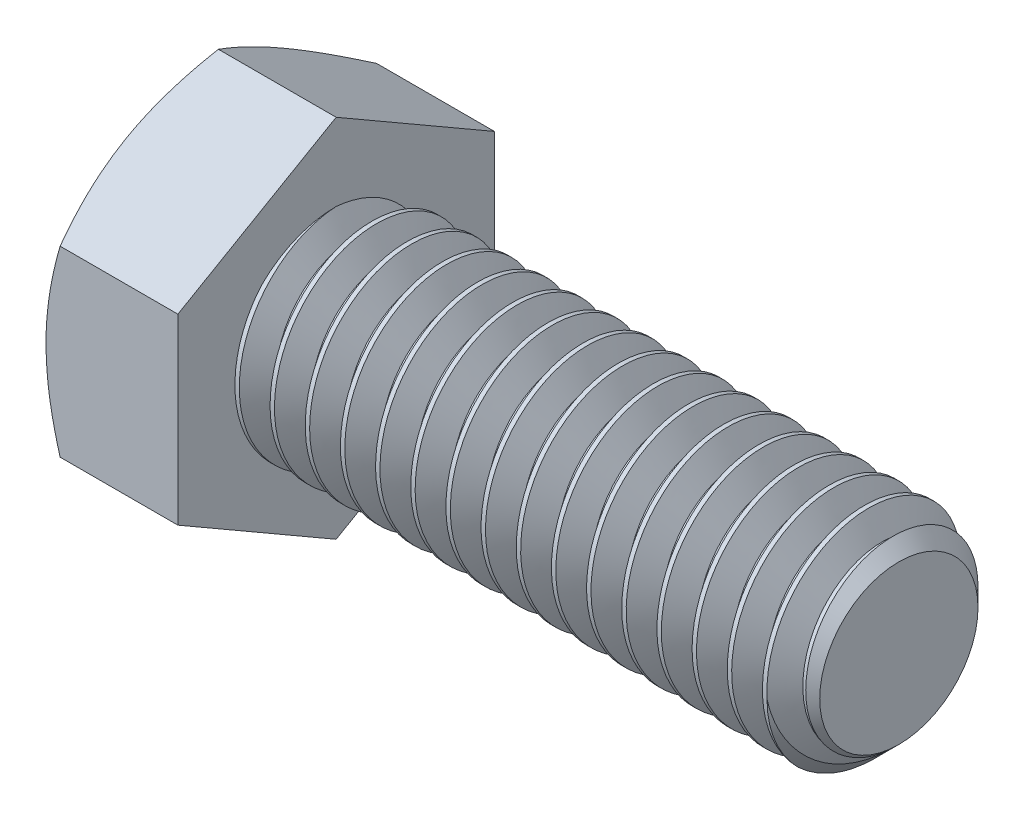
SolidWorks part; units mm, degrees
material "Stainless Steel (ferritic)"
ref_plane "Front Plane" through (0, 0, 0) normal (0, 0, 1) x (1, 0, 0)
ref_plane "Top Plane" through (0, 0, 0) normal (0, 1, 0) x (1, 0, 0)
ref_plane "Right Plane" through (0, 0, 0) normal (1, 0, 0) x (0, 0, -1)
sketch "Sketch1" plane through (0, 0, 0) normal (0, 0, 1) x (1, 0, 0)
  line L0 (-15.6766, 0) -> (15.6766, 0) construction
  line L1 (15.6766, 4.7625) -> (15.6766, -4.7625) construction
  line L2 (-9.7234, 7.1437) -> (-9.7234, -7.1437) construction
  line L3 (-15.6766, 7.1437) -> (-15.6766, -7.1437) construction
  point P9 (-9.7234, 0)
  point P10 (10.1203, -4.7625)
  dimension "D1" = 5.5562
  dimension "Screw Dia" = 9.525
  dimension "Hex" = 14.2875
  dimension "Head Ht" = 5.9531
  dimension "Screw Lenght" = 25.4
ref_plane "Plane2" through (15.6766, 0, 0) normal (1, 0, 0) x (0, 0, -1)
sketch "Sketch5" plane through (15.6766, 0, 0) normal (1, 0, 0) x (0, 0, -1)
  circle A0 centre (0, 0) radius 4.7625
extrude "Boss-Extrude3" add sketch "Sketch5" against normal up to vertex (25.4 mm away) up to point (-9.7234, 0, 0)
sketch "Sketch9" plane through (15.6766, 0, 0) normal (1, 0, 0) x (0, 0, -1)
  circle A1 centre (0, 0) radius 4.7625
  circle A2 centre (0, 0) radius 4.7625
  dimension "D1" = 0
curve "Helix/Spiral1" pitch 1.5875 height 26.9875 turns 17 parameters "Pitch"=1.5875
chamfer "Chamfer1" distance 1.1906 angle 45 1 edges at (15.6766, 0, -4.7625)
sketch "Sketch10" plane through (0, 0, 0) normal (0, 0, 1) x (1, 0, 0)
  line L0 (15.6766, 4.7625) -> (16.2719, 3.7314)
  line L1 (16.2719, 3.7314) -> (16.4703, 3.7314)
  line L2 (16.4703, 3.7314) -> (17.0656, 4.7625)
  line L3 (15.6766, 4.7625) -> (17.0656, 4.7625)
  line L4 (16.3711, 4.7625) -> (16.3711, 3.7314) construction
  line L5 (15.9742, 4.2469) -> (16.768, 4.2469) construction
  dimension "D1" = 60
  dimension "D2" = 0.1984
  dimension "D3" = 0.7937
sweep "Cut-Sweep1" cut profiles "Sketch10" path "Helix/Spiral1"
sketch "Sketch6" plane through (-9.7234, 0, 0) normal (-1, 0, 0) x (0, 0, 1)
  line L0 (0, 7.1437) -> (0, -7.1437) construction
  line L1 (7.1437, 4.1244) -> (0, 8.2489)
  line L2 (0, 8.2489) -> (-7.1437, 4.1244)
  line L3 (-7.1437, 4.1244) -> (-7.1437, -4.1244)
  line L4 (-7.1437, -4.1244) -> (0, -8.2489)
  line L5 (0, -8.2489) -> (7.1438, -4.1244)
  line L6 (7.1438, -4.1244) -> (7.1437, 4.1244)
  circle A0 centre (0, 0) radius 7.1438 construction
extrude "Boss-Extrude4" add sketch "Sketch6" along normal up to vertex (5.9531 mm away) up to point (-15.6766, -7.1437, 0)
sketch "Sketch7" plane through (-15.6766, 0, 0) normal (-1, 0, 0) x (0, 0, 1)
  circle A0 centre (0, 0) radius 7.1438 construction
  circle A1 centre (0, 0) radius 7.1438
sketch "Sketch8" plane through (-15.6766, 0, 0) normal (-1, 0, 0) x (0, 0, 1)
  circle A0 centre (0, 0) radius 7.1438 construction
  circle A1 centre (0, 0) radius 7.1438
extrude "Cut-Extrude3" cut sketch "Sketch8" against normal through all draft 60 flip side to cut
equation "\"D2@Sketch10\" = \"Pitch@Helix/Spiral1\"*.125"
equation "\"D3@Sketch10\" = \"Pitch@Helix/Spiral1\"*.5"
equation "\"D3@Helix/Spiral1\" = \"Screw Lenght@Sketch1\"+\"Pitch@Helix/Spiral1\""
equation "\"D1@Chamfer1\" = \"Pitch@Helix/Spiral1\"*.75"
equation "\"D1@Sketch1\" = \"Pitch@Helix/Spiral1\"*3.5"
